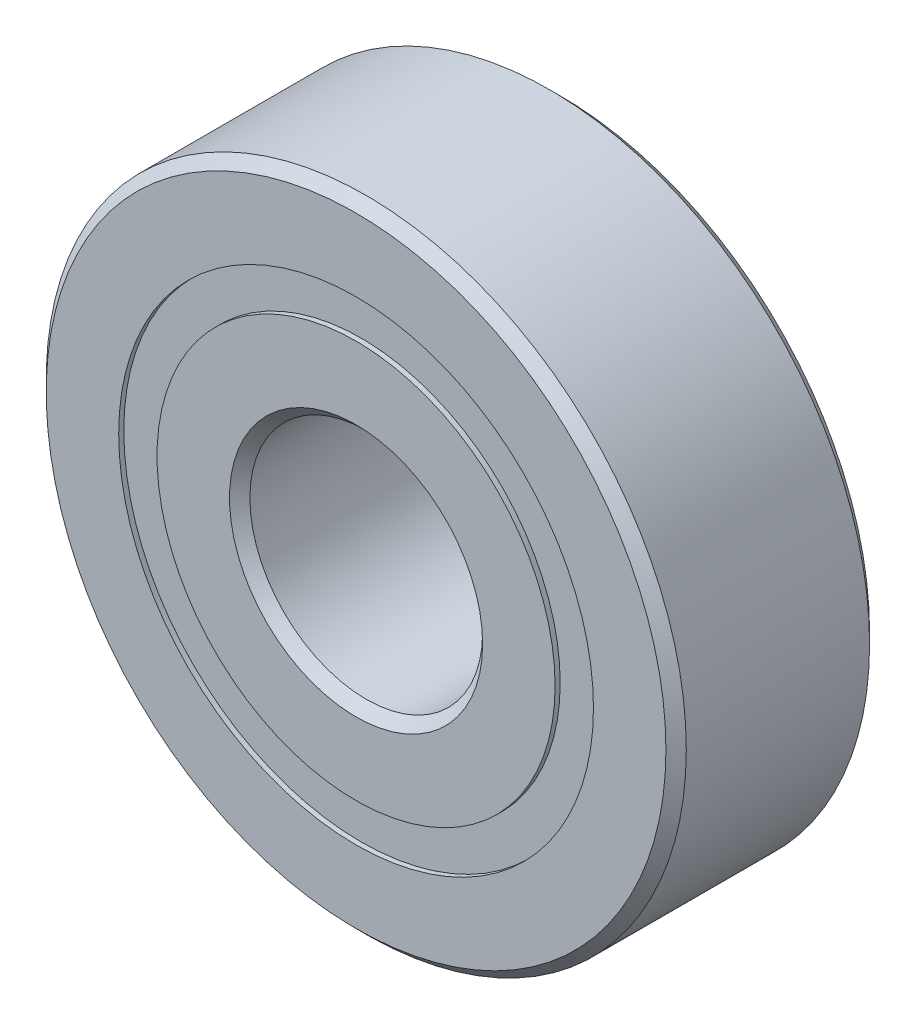
SolidWorks part; units mm, degrees
note: '?' marks a value the reader was unsure of.
material "AISI 316 Annealed Stainless Steel Bar (SS)"
ref_plane "Front Plane" through (0, 0, 0) normal (0, 0, 1) x (1, 0, 0)
ref_plane "Top Plane" through (0, 0, 0) normal (0, 1, 0) x (1, 0, 0)
ref_plane "Right Plane" through (0, 0, 0) normal (1, 0, 0) x (0, 0, -1)
sketch "Sketch1" plane through (0, 0, 0) normal (1, 0, 0) x (0, 0, -1)
  line L0 (-3.5, 0) -> (3.5, 0) construction
  line L1 (0, 11) -> (0, -11) construction
  line L2 (3.15, 11) -> (-3.15, 11)
  line L3 (-3.15, 11) -> (-3.5, 10.65)
  line L4 (-3.5, 10.65) -> (-3.5, 8.1593)
  line L5 (-3.5, 8.1593) -> (-1.5556, 8.1593)
  line L6 (3.5, 8.1593) -> (1.5556, 8.1593)
  line L7 (3.5, 10.65) -> (3.5, 8.1593)
  line L8 (3.15, 11) -> (3.5, 10.65)
  line L9 (0, 11) -> (0, 7.5) construction
  line L10 (0, 7.5) -> (0, 4) construction
  arc A0 (-1.5556, 8.1593) -> (1.5556, 8.1593) centre (0, 7.5) cw
  point P14 (0, 4)
  dimension "Width" = 7
  dimension "OD" = 22
  dimension "D1" = 45
  dimension "D2" = 0.35
  dimension "Shaft Dia" = 8
  dimension "D3" = 3.1111
  dimension "D4" = 0.6593
revolve "Revolve1" add sketch "Sketch1" angle 360 about L0
sketch "Sketch3" plane through (0, 0, 0) normal (1, 0, 0) x (0, 0, -1)
  line L0 (-3.5, 6.8407) -> (-1.5556, 6.8407)
  line L1 (0, 11) -> (0, -11) construction
  line L2 (-3.5, 10.65) -> (-3.5, 8.1593) construction
  line L3 (-3.5, 6.8407) -> (-3.5, 4.35)
  line L4 (-3.15, 11) -> (-3.5, 10.65) construction
  line L5 (-3.5, 4.35) -> (-3.15, 4)
  line L6 (-3.15, 4) -> (3.15, 4)
  line L7 (3.15, 11) -> (3.15, -11) construction
  line L8 (3.15, 4) -> (3.5, 4.35)
  line L9 (3.5, -10.65) -> (3.5, 10.65) construction
  line L10 (3.5, 4.35) -> (3.5, 6.8407)
  line L11 (3.5, 6.8407) -> (1.5556, 6.8407)
  line L13 (3.15, 11) -> (3.5, 10.65) construction
  arc A0 (1.5556, 8.1593) -> (-1.5556, 8.1593) centre (0, 7.5) ccw construction
  arc A1 (1.5556, 6.8407) -> (-1.5556, 6.8407) centre (0, 7.5) cw
revolve "Revolve3" add sketch "Sketch3" angle 360 about L0
sketch "Sketch4" plane through (0, 0, 0) normal (1, 0, 0) x (0, 0, -1)
  line L0 (-1.6895, 7.5) -> (1.6895, 7.5)
  arc A2 (-1.6895, 7.5) -> (1.6895, 7.5) centre (0, 7.5) cw
  arc A3 (1.5556, 8.1593) -> (-1.5556, 8.1593) centre (0, 7.5) ccw construction
revolve "Revolve4" add sketch "Sketch4" angle 360 about L0
ref_axis "Axis1" through (0, 0, -3.5) along (0, 0, 1)?
pattern_circular "CirPattern1" count 10 every 36 about axis through (0, 0, -3.5) along (0, 0, 1)
sketch "Sketch6" plane through (0, 0, 0) normal (1, 0, 0) x (0, 0, -1)
  line L0 (-3.5, 8.1593) -> (-1.5556, 8.1593) construction
  line L1 (-3.325, 8.1593) -> (-1.6895, 8.1593)
  line L2 (-3.325, 8.1593) -> (-3.325, 6.8407)
  line L3 (-3.325, 6.8407) -> (-1.6895, 6.8407)
  line L4 (-1.6895, 8.1593) -> (-1.6895, 6.8407)
  line L5 (-3.5, 6.8407) -> (-1.5556, 6.8407) construction
  line L6 (3.5, 8.1593) -> (1.5556, 8.1593) construction
  line L7 (3.325, 8.1593) -> (1.6895, 8.1593)
  line L8 (3.325, 8.1593) -> (3.325, 6.8407)
  line L9 (3.325, 6.8407) -> (1.6895, 6.8407)
  line L10 (1.6895, 8.1593) -> (1.6895, 6.8407)
  line L11 (3.5, 6.8407) -> (1.5556, 6.8407) construction
  line L12 (-3.15, 11) -> (-3.5, 10.65) construction
  point P18 (-3.325, 10.825)
revolve "Revolve5" add sketch "Sketch6" angle 360 about L0
equation "\"D2@Sketch1\" = \"Width@Sketch1\"*.05"
equation "\"D3@Sketch1\" = \"Width@Sketch1\"/2.25"
equation "\"D4@Sketch1\" = (((\"OD@Sketch1\"-\"Width@Sketch1\")/2)/3.25)/3.5"
equation "\"D2@CirPattern1\" = 360/\"Balls@CirPattern1\""
